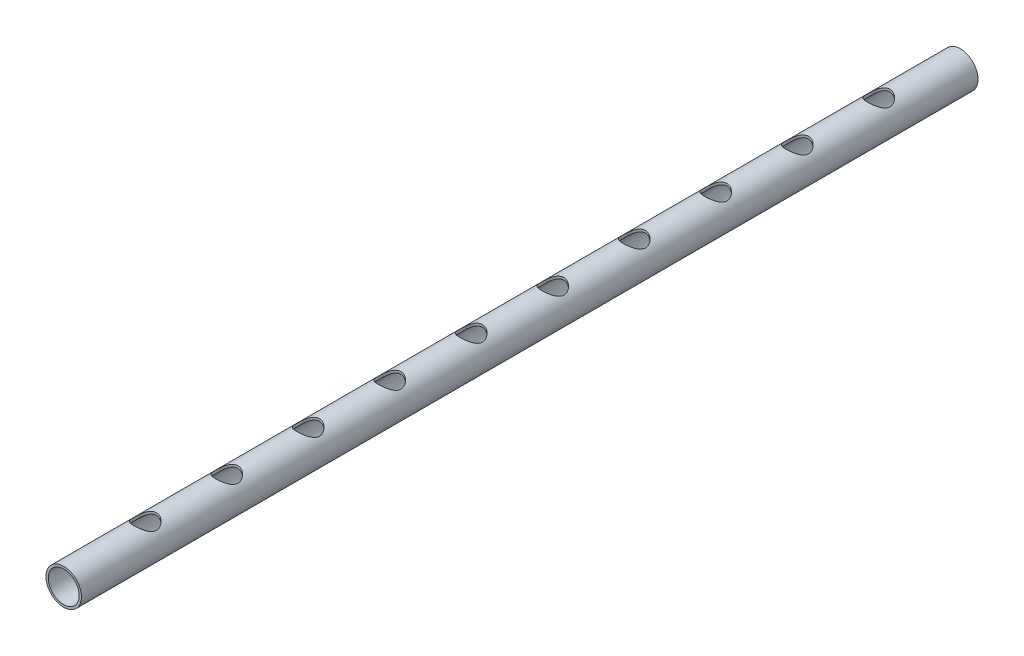
SolidWorks part; units mm, degrees
ref_plane "Front Plane" through (0, 0, 0) normal (0, 0, 1) x (1, 0, 0)
ref_plane "Top Plane" through (0, 0, 0) normal (0, 1, 0) x (1, 0, 0)
ref_plane "Right Plane" through (0, 0, 0) normal (1, 0, 0) x (0, 0, -1)
sketch "Sketch1" plane through (0, 0, 0) normal (0, 0, 1) x (1, 0, 0)
  circle A0 centre (0, 0) radius 30.1625
  circle A1 centre (0, 0) radius 26.2509
  dimension "D1" = 60.325
  dimension "D2" = 3.9116
extrude "Boss-Extrude1" add sketch "Sketch1" along normal blind 1524
sketch "Sketch2" plane through (0, 0, 0) normal (0, 0, -1) x (-1, 0, 0)
  line L0 (-30.1625, 0) -> (30.1625, 0)
  circle A0 centre (0, 0) radius 30.1625 construction
ref_axis "Axis2" through (0, 0, 1524) along (0, 0, -1)
ref_plane "Plane2" through (0, 0, 0) normal (0, 1, 0) x (1, 0, 0)
sketch "Sketch3" plane through (0, 0, 0) normal (0, 1, 0) x (1, 0, 0)
  line L0 (0, 0) -> (0, -138.5455) construction
  line L1 (0, -138.5455) -> (0, -277.0909) construction
  line L2 (0, -277.0909) -> (0, -415.6364) construction
  line L3 (0, -415.6364) -> (0, -554.1818) construction
  line L4 (0, -554.1818) -> (0, -692.7273) construction
  line L5 (0, -692.7273) -> (0, -831.2727) construction
  line L6 (0, -831.2727) -> (0, -969.8182) construction
  line L7 (0, -969.8182) -> (0, -1108.3636) construction
  line L8 (0, -1108.3636) -> (0, -1246.9091) construction
  line L9 (0, -1246.9091) -> (0, -1385.4545) construction
  line L10 (0, -1385.4545) -> (0, -1524) construction
  line L11 (-30.1625, -1524) -> (30.1625, -1524) construction
  circle A0 centre (0, -138.5455) radius 19.05
  circle A1 centre (0, -277.0909) radius 19.05
  circle A2 centre (0, -415.6364) radius 19.05
  circle A3 centre (0, -554.1818) radius 19.05
  circle A4 centre (0, -692.7273) radius 19.05
  circle A5 centre (0, -831.2727) radius 19.05
  circle A6 centre (0, -969.8182) radius 19.05
  circle A7 centre (0, -1108.3636) radius 19.05
  circle A8 centre (0, -1246.9091) radius 19.05
  circle A9 centre (0, -1385.4545) radius 19.05
  dimension "D1" = 38.1
extrude "Cut-Extrude1" cut sketch "Sketch3" against normal blind 5.08 and the other way through all
